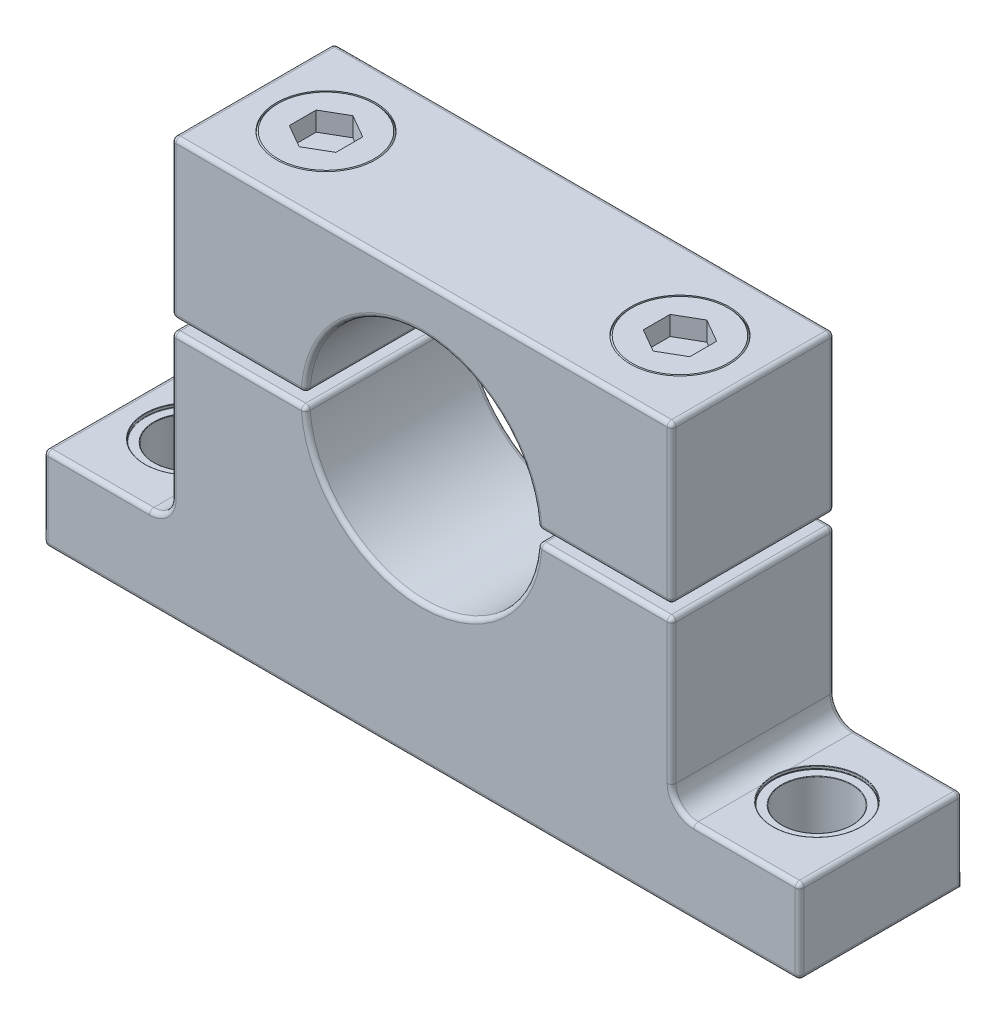
SolidWorks part; units mm, degrees
ref_plane "Front" through (0, 0, 0) normal (0, 0, 1) x (1, 0, 0)
ref_plane "Top" through (0, 0, 0) normal (0, 1, 0) x (1, 0, 0)
ref_plane "Right" through (0, 0, 0) normal (1, 0, 0) x (0, 0, -1)
sketch "Sketch1" plane through (0, 0, 0) normal (0, 0, 1) x (1, 0, 0)
  line L0 (0, 36) -> (0, 0) construction
  line L1 (-32.5, 0) -> (32.5, 0) construction
  line L2 (0, 0) -> (0, 22) construction
  line L3 (-27, 0) -> (27, 0) construction
  line L4 (24, 0) -> (30, 0) construction
  line L5 (30, 0) -> (30, 1.27) construction
  line L6 (24, 0) -> (24, 1.27) construction
  line L7 (-24, 0) -> (-24, 1.27) construction
  line L8 (-30, 0) -> (-30, 1.27) construction
  line L9 (-24, 0) -> (-30, 0) construction
  line L10 (-21.5, 22) -> (21.5, 22) construction
  line L11 (-21.5, 21.492) -> (21.5, 21.492) construction
  line L12 (-21.5, 22.508) -> (21.5, 22.508) construction
  line L13 (23.619, 0) -> (23.619, 1.27) construction
  line L14 (30.381, 0) -> (30.381, 1.27) construction
  line L15 (-23.619, 0) -> (-23.619, 1.27) construction
  line L16 (-30.381, 0) -> (-30.381, 1.27) construction
  line L17 (-11.0713, 21.492) -> (11.0713, 21.492) construction
  line L18 (-11.0713, 22.508) -> (11.0713, 22.508) construction
  line L19 (-11.0713, 22) -> (11.0713, 22) construction
  line L20 (-32.5, 0) -> (-32.5, 7.2) construction
  line L21 (-32.5, 7.2) -> (-21.5, 7.2) construction
  line L22 (-21.5, 21.492) -> (-21.5, 7.2) construction
  line L23 (-21.5, 22.508) -> (-21.5, 36) construction
  line L24 (-21.5, 36) -> (21.5, 36) construction
  line L25 (32.5, 0) -> (32.5, 7.2) construction
  line L26 (32.5, 7.2) -> (21.5, 7.2) construction
  line L27 (21.5, 21.492) -> (21.5, 7.2) construction
  line L28 (21.5, 22.508) -> (21.5, 36) construction
  line L29 (0, 36) -> (0, 31) construction
  line L30 (0.3175, 31) -> (-0.3175, 31) construction
  line L31 (21.5, 7.2) -> (21.5, 0) construction
  circle A0 centre (0, 22) radius 10 construction
  arc A1 (-23.405, 7.2) -> (-21.5, 9.105) centre (-23.405, 9.105) ccw construction
  arc A2 (23.405, 7.2) -> (21.5, 9.105) centre (23.405, 9.105) cw construction
  point P5 (0, 0)
  point P9 (0, 22)
  point P11 (0, 0)
  point P12 (27, 0)
  point P13 (-27, 0)
  point P16 (27, 0)
  point P37 (0, 21.492)
  point P40 (0, 22.508)
  point P60 (0, 31)
  point P64 (27, 7.2)
  dimension "D1" = 1.27
  dimension "D8" = 7.2
  dimension "D12" = 0.635
  dimension "D10" = 1.905
  dimension "D11" = 1.905
  dimension "D9" = 5.5
  dimension "D13" = 5.5
  dimension "D2" = 0.508
  dimension "D3" = 0.508
  dimension "D4" = 0.381
  dimension "D5" = 0.381
  dimension "D6" = 0.381
  dimension "D7" = 0.381
sketch "Sketch3" plane through (0, 0, 0) normal (0, 0, 1) x (1, 0, 0)
  line L0 (-21.5, 36) -> (21.5, 36) construction
  line L1 (21.5, 22.508) -> (21.5, 36) construction
  line L2 (-21.5, 22.508) -> (21.5, 22.508) construction
  line L3 (-21.5, 22.508) -> (-21.5, 36) construction
  line L4 (-21.5, 21.492) -> (-21.5, 7.2) construction
  line L5 (-32.5, 7.2) -> (-21.5, 7.2) construction
  line L6 (-32.5, 0) -> (-32.5, 7.2) construction
  line L7 (-32.5, 0) -> (32.5, 0) construction
  line L8 (32.5, 0) -> (32.5, 7.2) construction
  line L9 (32.5, 7.2) -> (21.5, 7.2) construction
  line L10 (21.5, 21.492) -> (21.5, 7.2) construction
  line L11 (-21.5, 21.492) -> (21.5, 21.492) construction
  line L12 (-21.5, 36) -> (21.5, 36)
  line L13 (21.5, 22.508) -> (21.5, 36)
  line L14 (-21.5, 22.508) -> (-9.9871, 22.508)
  line L15 (-21.5, 22.508) -> (-21.5, 36)
  line L16 (-21.5, 21.492) -> (-21.5, 9.105)
  line L17 (-32.5, 7.2) -> (-23.405, 7.2)
  line L18 (-32.5, 0) -> (-32.5, 7.2)
  line L19 (-32.5, 0) -> (32.5, 0)
  line L20 (32.5, 0) -> (32.5, 7.2)
  line L21 (32.5, 7.2) -> (23.405, 7.2)
  line L22 (21.5, 21.492) -> (21.5, 9.105)
  line L23 (-21.5, 21.492) -> (-9.9871, 21.492)
  line L24 (9.9871, 22.508) -> (21.5, 22.508)
  line L25 (9.9871, 21.492) -> (21.5, 21.492)
  arc A0 (-23.405, 7.2) -> (-21.5, 9.105) centre (-23.405, 9.105) ccw construction
  arc A1 (21.5, 9.105) -> (23.405, 7.2) centre (23.405, 9.105) ccw construction
  circle A2 centre (0, 22) radius 10 construction
  arc A3 (-23.405, 7.2) -> (-21.5, 9.105) centre (-23.405, 9.105) ccw
  arc A4 (21.5, 9.105) -> (23.405, 7.2) centre (23.405, 9.105) ccw
  arc A5 (9.9871, 22.508) -> (-9.9871, 22.508) centre (0, 22) ccw
  arc A6 (-9.9871, 21.492) -> (9.9871, 21.492) centre (0, 22) ccw
extrude "Boss-Extrude1" add sketch "Sketch3" against normal blind 14
sketch "Sketch4" plane through (0, 0, 0) normal (0, -1, 0) x (1, 0, 0)
  line L0 (-32.5, 0) -> (-32.5, -14) construction
  line L1 (-32.5, 0) -> (-21.5, 0) construction
  line L2 (-32.5, -7) -> (32.5, -7) construction
  line L3 (32.5, -14) -> (32.5, 0) construction
  line L4 (-27, 0) -> (-27, -14) construction
  line L5 (27, 0) -> (27, -14) construction
  line L6 (-32.5, -14) -> (32.5, -14) construction
  line L7 (0, 0) -> (0, -14) construction
  circle A0 centre (-27, -7) radius 3
  circle A1 centre (27, -7) radius 3
  point P7 (-32.5, -7)
  dimension "D1" = 6
extrude "Cut-Extrude1" cut sketch "Sketch4" against normal through all
sketch "Sketch6" plane through (0, 7.2, 0) normal (0, 1, 0) x (1, 0, 0)
  line L0 (0, 0) -> (0, 14) construction
  line L1 (-32.5, 0) -> (32.5, 0) construction
  line L2 (21.5, 14) -> (-21.5, 14) construction
  circle A1 centre (-27, 7) radius 3 construction
  circle A2 centre (-27, 7) radius 3
  circle A4 centre (-27, 7) radius 3.381
  circle A5 centre (27, 7) radius 3.381
  dimension "D1" = 0.381
sketch "Sketch7" plane through (0, 0, 0) normal (0, 0, 1) x (1, 0, 0)
  line L0 (-32.5, 6.946) -> (32.5, 6.946) construction
  line L1 (-21.5, 21.492) -> (-21.5, 0) construction
  line L2 (-32.5, 0) -> (32.5, 0) construction
  line L3 (21.5, 21.492) -> (21.5, 0) construction
  line L5 (-32.5, 0) -> (-32.5, 7.2) construction
  line L6 (-32.5, 7.2) -> (-21.5, 7.2) construction
  line L7 (32.5, 0) -> (32.5, 7.2) construction
  line L8 (-27, 7.2) -> (-27, 6.946) construction
  line L9 (27, 7.2) -> (27, 6.946) construction
  line L10 (32.5, 7.2) -> (21.5, 7.2) construction
  dimension "D1" = 0.254
sketch "Sketch8" plane through (0, 21.492, 0) normal (0, 1, 0) x (1, 0, 0)
  line L0 (0, 0) -> (0, 14) construction
  line L1 (21.5, 14) -> (-21.5, 14) construction
  circle A0 centre (-27, 7) radius 3.381 construction
  circle A1 centre (27, 7) radius 3.381 construction
  circle A2 centre (-27, 7) radius 3.381 construction
  circle A3 centre (27, 7) radius 3.381 construction
  circle A4 centre (-27, 7) radius 3.762
  circle A5 centre (27, 7) radius 3.762
  dimension "D1" = 0.381
extrude "Cut-Extrude3" cut sketch "Sketch8" against normal up to vertex (14.546 mm away) up to point (-27, 6.946, 0)
sketch "Sketch10" plane through (0, 36, 0) normal (0, 1, 0) x (1, 0, 0)
  line L0 (-21.5, 14) -> (-21.5, 0) construction
  line L1 (21.5, 14) -> (21.5, 0) construction
  line L2 (-21.5, 14) -> (-21.5, 0) construction
  line L3 (21.5, 14) -> (21.5, 0) construction
  line L4 (-19.468, 14) -> (-19.468, 0) construction
  line L5 (0, 0) -> (0, 14) construction
  line L6 (19.468, 14) -> (19.468, 0) construction
  circle A0 centre (-15.218, 7) radius 2.5 construction
  circle A1 centre (15.218, 7) radius 2.754
  circle A2 centre (-15.218, 7) radius 2.754
  circle A3 centre (15.218, 7) radius 2.5 construction
  circle A4 centre (-15.218, 7) radius 4.25 construction
  circle A5 centre (15.218, 7) radius 4.25 construction
  dimension "D1" = 2.032
  dimension "D3" = 0.254
extrude "Cut-Extrude4" cut sketch "Sketch10" against normal through all
ref_plane "Plane1" through (0, 0, -7) normal (0, 0, 1) x (1, 0, 0)
sketch "Sketch12" plane through (0, 36, 0) normal (0, 1, 0) x (1, 0, 0)
  line L0 (0, 14) -> (0, 0) construction
  circle A0 centre (-15.218, 7) radius 4.1355 construction
  circle A1 centre (15.218, 7) radius 4.2625
  circle A2 centre (-15.218, 7) radius 4.2625
  circle A3 centre (15.218, 7) radius 4.1355 construction
  dimension "D2" = 8.525
extrude "Cut-Extrude5" cut sketch "Sketch12" against normal blind 5.015
sketch "Sketch13" plane through (0, 0, 0) normal (0, 1, 0) x (1, 0, 0)
  line L0 (-15.218, 14) -> (-15.218, 0) construction
  line L1 (21.5, 14) -> (-21.5, 14) construction
  line L2 (0, 14) -> (0, 0) construction
  line L3 (15.218, 14) -> (15.218, 0) construction
  circle A0 centre (-15.218, 7) radius 2.0066 construction
  point P2 (-15.218, 7)
  point P9 (-15.218, 14)
  point P10 (-15.218, 0)
  point P17 (15.218, 14)
  point P18 (15.218, 0)
sketch "Sketch15" plane through (0, 0, -7) normal (0, 0, 1) x (1, 0, 0)
  line L0 (-15.218, 6.946) -> (-15.218, 36) construction
  line L1 (-15.218, 36) -> (-19.468, 36) construction
  line L2 (-19.468, 36) -> (-19.468, 31) construction
  line L3 (-19.468, 31) -> (-17.718, 31) construction
  line L4 (-17.718, 31) -> (-17.718, 6.946) construction
  line L5 (-17.718, 6.946) -> (-15.218, 6.946) construction
  line L6 (-32.5, 6.946) -> (32.5, 6.946) construction
  line L8 (-21.5, 36) -> (21.5, 36) construction
  line L9 (-15.218, 6.946) -> (-15.218, 36)
  line L10 (-15.218, 36) -> (-19.468, 36)
  line L11 (-19.468, 36) -> (-19.468, 31)
  line L12 (-19.468, 31) -> (-17.718, 31)
  line L13 (-17.718, 31) -> (-17.718, 6.946)
  line L14 (-17.718, 6.946) -> (-15.218, 6.946)
  dimension "D2" = 4.25
  dimension "D1" = 5
  dimension "D3" = 2.5
revolve "Revolve1" add sketch "Sketch15" angle 360 about L9
chamfer "Chamfer1" distance 0.127 angle 45 1 edges at (-15.218, 36, -11.25)
sketch "Sketch16" plane through (0, 36, 0) normal (0, 1, 0) x (1, 0, 0)
  line L0 (-15.218, 14) -> (-15.218, 0) construction
  line L1 (-15.218, 9.3094) -> (-17.218, 8.1547)
  line L2 (-17.218, 8.1547) -> (-17.218, 5.8453)
  line L3 (-17.218, 5.8453) -> (-15.218, 4.6906)
  line L4 (-15.218, 4.6906) -> (-13.218, 5.8453)
  line L5 (-13.218, 5.8453) -> (-13.218, 8.1547)
  line L6 (-13.218, 8.1547) -> (-15.218, 9.3094)
  circle A0 centre (-15.218, 7) radius 2 construction
  dimension "Hex Size" = 4
extrude "Cut-Extrude6" cut sketch "Sketch16" against normal blind 1.65
mirror "Mirror1" about plane through (0, 0, 0) normal (1, 0, 0) of bodies 121 119
fillet "Fillet1" radius 0.381 18 edges at (0, 36, -14) (-21.5, 36, -7) (-21.5, 29.254, -14) (-21.5, 29.254, 0) (21.5, 29.254, -14) (21.5, 36, -7) (21.5, 29.254, 0) (0, 36, 0) (21.5, 22.508, -7) (15.7435, 22.508, -14) (-15.7435, 22.508, -14) (-21.5, 22.508, -7) (-15.7435, 22.508, 0) (15.7435, 22.508, 0) (0, 32, -14) (0, 32, 0) (9.9871, 22.508, -7) (-9.9871, 22.508, -7)
fillet "Fillet2" radius 0.381 31 edges at (27.9525, 7.2, -14) (22.058, 7.758, -14) (21.5, 15.2985, 0) (22.058, 7.758, 0) (-27.9525, 7.2, 0) (-22.058, 7.758, 0) (-27.9525, 7.2, -14) (-22.058, 7.758, -14) (21.5, 15.2985, -14) (32.5, 0, -7) (32.5, 3.6, -14) (32.5, 7.2, -7) (27.9525, 7.2, 0) (32.5, 3.6, 0) (0, 0, 0) (-32.5, 3.6, -14) (-32.5, 0, -7) (-32.5, 7.2, -7) (-32.5, 3.6, 0) (-21.5, 15.2985, 0) (-21.5, 15.2985, -14) (21.5, 21.492, -7) (-21.5, 21.492, -7) (-15.7435, 21.492, 0) (15.7435, 21.492, 0) (15.7435, 21.492, -14) (-15.7435, 21.492, -14) (0, 12, -14) (0, 12, 0) (9.9871, 21.492, -7) (-9.9871, 21.492, -7)
fillet "Fillet3" radius 0.0381 8 edges at (-30.762, 6.946, -7) (30.762, 6.946, -7) (30.762, 7.2, -7) (23.2619, 7.2054, -6.577) (30, 6.946, -7) (-23.2407, 7.2071, -7.1427) (-30.762, 7.2, -7) (-30, 6.946, -7)
sketch "Sketch17" plane through (0, 0, 0) normal (0, 0, 1) x (1, 0, 0)
  line L0 (0, 36) -> (0, 0.381) construction
  line L1 (-21.119, 36) -> (21.119, 36) construction
  line L2 (-32.119, 0.381) -> (32.119, 0.381) construction
  line L3 (-21.5, 18.1905) -> (21.5, 18.1905) construction
  line L4 (-21.5, 9.105) -> (-21.5, 21.111) construction
  line L5 (21.5, 21.111) -> (21.5, 9.105) construction
  point P8 (0, 18.1905)
ref_plane "Contact Plane 1" through (0, 36, 0) normal (0, 1, 0) x (1, 0, 0)
ref_plane "Contact Plane 2" through (0, 0, 0) normal (0, -1, 0) x (-1, 0, 0)
ref_plane "Contact Plane 3" through (-32.5, 0, 0) normal (-1, 0, 0) x (0, 0, 1)
ref_plane "Contact Plane 4" through (32.5, 0, 0) normal (1, 0, 0) x (0, 0, -1)
ref_plane "Contact Plane 5" through (0, 0, 0) normal (0, 0, 1) x (1, 0, 0)
ref_plane "Contact Plane 6" through (0, 0, -14) normal (0, 0, -1) x (-1, 0, 0)
ref_plane "Contact Plane 7" through (0, 18, 0) normal (0, -1, 0) x (-1, 0, 0)
ref_plane "Contact Plane 8" through (0, 0, 0) normal (-1, 0, 0) x (0, 0, 1)
ref_plane "Contact Plane 9" through (0, 0, -7) normal (0, 0, -1) x (-1, 0, 0)
ref_axis "Center Axis 1" through (0, 18, -14.2809) along (0, 0, 1)
ref_axis "Center Axis 2" through (23.2309, 18, -7) along (-1, 0, 0)
ref_axis "Center Axis 3" through (0, 22.2525, -7) along (0, 1, 0)
equation "\"D8@Sketch1\"=\"Oall Ht@Sketch1\"*.20"
equation "\"D1@Sketch4\"= \"HoldDia@Sketch1\""
equation "\"D1@Cut-Extrude5\"=\"HeadDp@Sketch1\"+.015"
equation "\"D1@Sketch15\"=\"HeadDp@Sketch1\""
equation "\"D3@Sketch15\"=\"ThrdDia@Sketch10\"*.5"
equation "\"D1@Cut-Extrude6\"= \"HeadDp@Sketch1\"*.33"
equation "\"D2@Sketch12\"=\"Head Dia@Sketch10\"+.025"
equation "\"D2@Sketch15\"=\"Head Dia@Sketch10\"*.50"
equation "\"D13@Sketch1\"=\"D9@Sketch1\""
